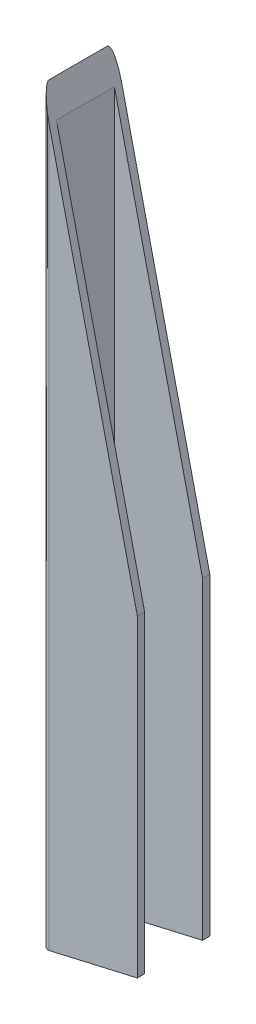
SolidWorks part; units mm, degrees
ref_plane "Спереди" through (0, 0, 0) normal (0, 0, 1) x (1, 0, 0)
ref_plane "Сверху" through (0, 0, 0) normal (0, 1, 0) x (1, 0, 0)
ref_plane "Справа" through (0, 0, 0) normal (1, 0, 0) x (0, 0, -1)
sketch "Эскиз1" plane through (0, 0, 0) normal (0, 1, 0) x (1, 0, 0)
  line L1 (-37, 15) -> (37, 15)
  line L2 (-40, 12) -> (-40, -12)
  line L3 (-37, -15) -> (37, -15)
  line L4 (40, 12) -> (40, -12)
  line L5 (-40, 15) -> (40, -15) construction
  line L6 (-40, -15) -> (40, 15) construction
  arc A0 (-37, 15) -> (-40, 12) centre (-37, 12) ccw
  arc A1 (-40, -12) -> (-37, -15) centre (-37, -12) ccw
  arc A2 (37, -15) -> (40, -12) centre (37, -12) ccw
  arc A3 (37, 15) -> (40, 12) centre (37, 12) cw
  point P0 (0, 0)
  dimension "D1" = 3
extrude "Вытянуть-Тонкостенный1" add sketch "Эскиз1" along normal blind 310 thin thin type one direction reverse wall 3
sketch "Эскиз2" plane through (0, 310, 0) normal (0, 1, 0) x (1, 0, 0)
  line L1 (-0.5, -21.5541) -> (41.1465, -21.5541)
  line L2 (-0.5, -21.5541) -> (-0.5, 20.9728)
  line L3 (-0.5, 20.9728) -> (41.1465, 20.9728)
  line L4 (41.1465, -21.5541) -> (41.1465, 20.9728)
extrude "Вырез-Вытянуть1" cut sketch "Эскиз2" against normal through all
sketch "Эскиз3" plane through (0, 0, 15) normal (0, 0, 1) x (1, 0, 0)
  line L0 (-40, 310) -> (-0.5, 138.9067)
  line L1 (-0.5, 0) -> (-0.5, 310) construction
  line L2 (-0.5, 138.9067) -> (-0.5, 9.1193)
  line L3 (-0.5, 9.1193) -> (-40, 0)
  line L4 (-40, 0) -> (-40, 310)
  line L5 (85.9225, 29.0715) -> (-60.233, -4.6711) construction
  line L6 (-0.5, 310) -> (-0.5, 0) construction
extrude "Вырез-Вытянуть2" cut sketch "Эскиз3" against normal through all flip side to cut
